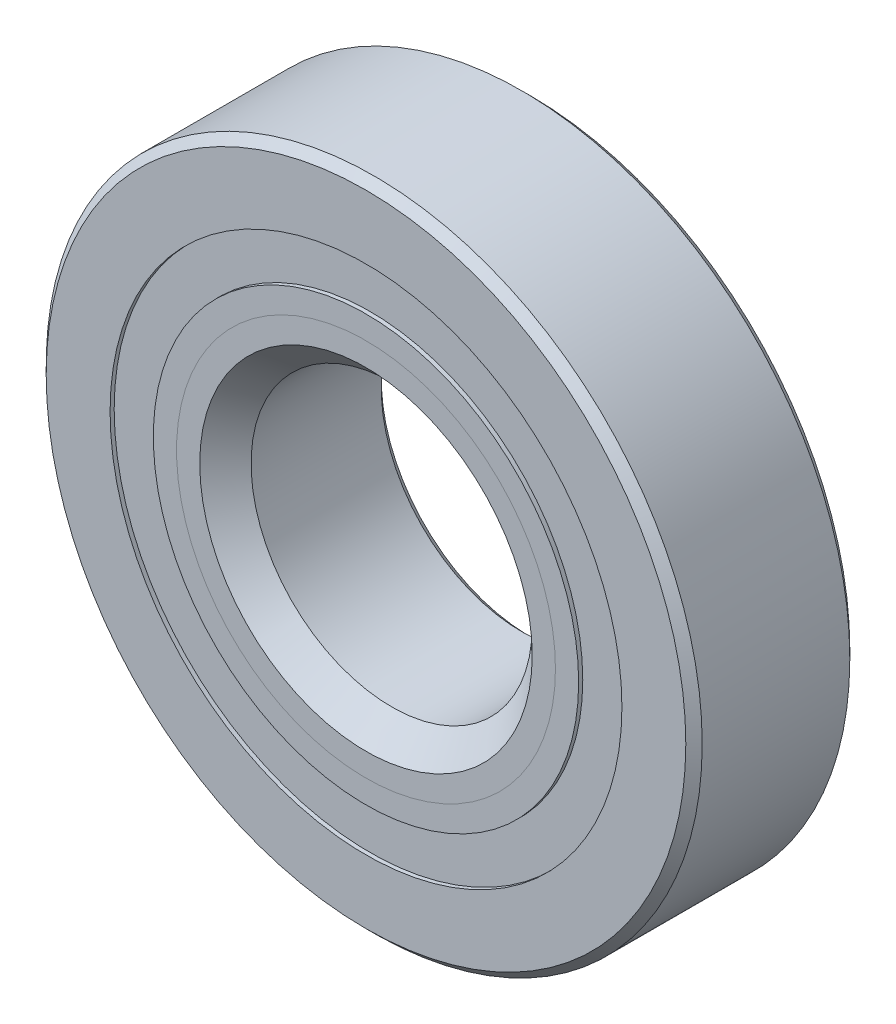
SolidWorks part; units mm, degrees
ref_plane "Front Plane" through (0, 0, 0) normal (0, 0, 1) x (1, 0, 0)
ref_plane "Top Plane" through (0, 0, 0) normal (0, 1, 0) x (1, 0, 0)
ref_plane "Right Plane" through (0, 0, 0) normal (1, 0, 0) x (0, 0, -1)
sketch "Sketch1" plane through (0, 0, 0) normal (1, 0, 0) x (0, 0, -1)
  line L0 (-2.7781, 0) -> (2.7781, 0) construction
  line L1 (0, 11.1125) -> (0, -11.1125) construction
  line L2 (2.5003, 11.1125) -> (-2.5003, 11.1125)
  line L3 (-2.5003, 11.1125) -> (-2.7781, 10.8347)
  line L4 (-2.7781, 10.8347) -> (-2.7781, 8.6702)
  line L5 (-2.7781, 8.6702) -> (-1.2347, 8.6702)
  line L6 (2.7781, 8.6702) -> (1.2347, 8.6702)
  line L7 (2.7781, 10.8347) -> (2.7781, 8.6702)
  line L8 (2.5003, 11.1125) -> (2.7781, 10.8347)
  line L9 (0, 11.1125) -> (0, 7.9375) construction
  line L10 (0, 7.9375) -> (0, 4.7625) construction
  arc A0 (-1.2347, 8.6702) -> (1.2347, 8.6702) centre (0, 7.9375) cw
  point P14 (0, 4.7625)
  dimension "D3" = 2.4694
  dimension "D1" = 45
  dimension "Width" = 5.5562
  dimension "OD" = 22.225
  dimension "D2" = 0.2778
  dimension "Shaft Dia" = 9.525
  dimension "D4" = 0.7327
revolve "Revolve1" add sketch "Sketch1" angle 360 about L0
sketch "Sketch2" plane through (0, 0, 0) normal (1, 0, 0) x (0, 0, -1)
  line L0 (-2.7781, 7.2048) -> (-1.2347, 7.2048)
  line L1 (-2.7781, 10.8347) -> (-2.7781, -10.8347) construction
  line L2 (-2.7781, 7.2048) -> (-2.7781, 6.4185)
  line L3 (-2.7781, 6.4185) -> (-1.9918, 5.6321)
  line L4 (-1.9918, 5.6321) -> (0, 5.6321)
  line L5 (0, 11.1125) -> (0, -11.1125) construction
  line L6 (0, 5.6321) -> (0, 6.5018)
  line L7 (0, 6.5018) -> (0, 4.7625) construction
  line L8 (-2.7781, 7.2048) -> (-2.7781, 5.6321) construction
  line L9 (-2.7781, 5.6321) -> (-1.9918, 5.6321) construction
  arc A0 (-1.2347, 7.2048) -> (0, 6.5018) centre (0, 7.9375) ccw
  arc A1 (1.2347, 8.6702) -> (-1.2347, 8.6702) centre (0, 7.9375) ccw construction
  circle A2 centre (0, 7.9375) radius 1.4357 construction
  dimension "D1" = 45
revolve "Revolve2" add sketch "Sketch2" angle 360 about L0
sketch "Sketch3" plane through (0, 0, 0) normal (1, 0, 0) x (0, 0, -1)
  line L0 (-2.7781, 6.4185) -> (-1.9918, 5.6321)
  line L1 (-1.9918, 5.6321) -> (0, 5.6321)
  line L2 (0, 5.6321) -> (0, 6.5018)
  line L3 (-2.7781, 6.4185) -> (-2.7781, 5.6321)
  line L4 (-2.7781, 7.2048) -> (-2.7781, 5.6321) construction
  line L5 (-2.7781, 5.6321) -> (-1.9085, 4.7625)
  line L6 (-1.9085, 4.7625) -> (2.5003, 4.7625)
  line L7 (2.5003, 11.1125) -> (2.5003, -11.1125) construction
  line L8 (2.5003, 4.7625) -> (2.7781, 5.0403)
  line L9 (2.7781, -10.8347) -> (2.7781, 10.8347) construction
  line L10 (2.7781, 5.0403) -> (2.7781, 7.2048)
  line L11 (2.7781, 7.2048) -> (1.2347, 7.2048)
  line L13 (2.5003, 11.1125) -> (2.7781, 10.8347) construction
  circle A0 centre (0, 7.9375) radius 1.4357 construction
  arc A1 (1.2347, 7.2048) -> (0, 6.5018) centre (0, 7.9375) cw
revolve "Revolve3" add sketch "Sketch3" angle 360 about L0
sketch "Sketch4" plane through (0, 0, 0) normal (1, 0, 0) x (0, 0, -1)
  line L0 (-1.4357, 7.9375) -> (1.4357, 7.9375)
  circle A1 centre (0, 7.9375) radius 1.4357 construction
  arc A2 (-1.4357, 7.9375) -> (1.4357, 7.9375) centre (0, 7.9375) cw
  arc A3 (1.2347, 8.6702) -> (-1.2347, 8.6702) centre (0, 7.9375) ccw construction
revolve "Revolve4" add sketch "Sketch4" angle 360 about L0
ref_axis "Axis1" through (0, 0, -2.7781) along (0, 0, 1)
pattern_circular "CirPattern1" count 12 every 30 about axis through (0, 0, -2.7781) along (0, 0, 1) of bodies 104
sketch "Sketch5" plane through (0, 0, 0) normal (1, 0, 0) x (0, 0, -1)
  line L0 (-2.6392, 8.6702) -> (-2.6392, 10.9736) construction
  line L1 (-2.6392, 8.6702) -> (-1.4357, 8.6702)
  line L2 (-2.6392, 8.6702) -> (-2.6392, 7.2048)
  line L3 (-2.6392, 7.2048) -> (-1.4357, 7.2048)
  line L4 (-1.4357, 8.6702) -> (-1.4357, 7.2048)
  line L5 (1.4357, 8.6702) -> (2.6392, 8.6702)
  line L6 (1.4357, 8.6702) -> (1.4357, 7.2048)
  line L7 (1.4357, 7.2048) -> (2.6392, 7.2048)
  line L8 (2.6392, 8.6702) -> (2.6392, 7.2048)
  line L9 (-2.5003, 11.1125) -> (-2.7781, 10.8347) construction
  line L10 (-2.7781, 8.6702) -> (-1.2347, 8.6702) construction
  line L11 (-2.7781, 7.2048) -> (-1.2347, 7.2048) construction
  circle A0 centre (0, 7.9375) radius 1.4357 construction
revolve "Revolve5" add sketch "Sketch5" angle 360 about L0
equation "\"D2@Sketch1\" = \"Width@Sketch1\"*.05"
equation "\"D3@Sketch1\" = \"Width@Sketch1\"/2.25"
equation "\"D4@Sketch1\" = (((\"OD@Sketch1\"-\"Width@Sketch1\")/2)/3.25)/3.5"
equation "\"D2@CirPattern1\" = 360/\"Balls@CirPattern1\""
